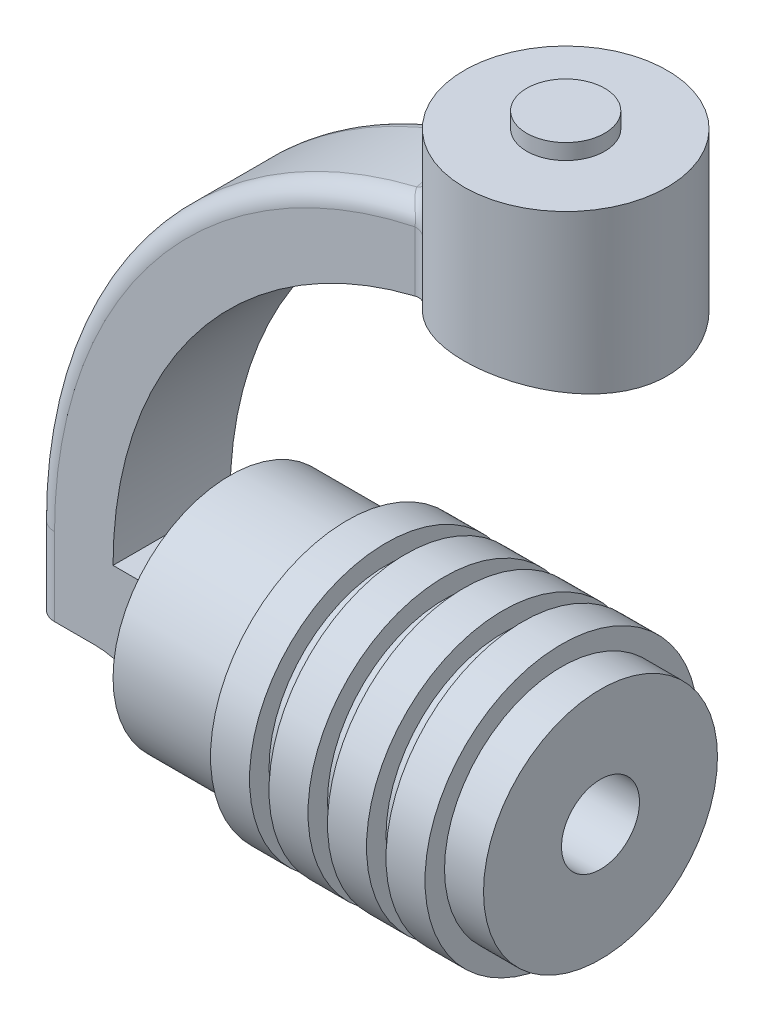
SolidWorks part; units mm, degrees
ref_plane "Front Plane" through (0, 0, 0) normal (0, 0, 1) x (1, 0, 0)
ref_plane "Top Plane" through (0, 0, 0) normal (0, 1, 0) x (1, 0, 0)
ref_plane "Right Plane" through (0, 0, 0) normal (1, 0, 0) x (0, 0, -1)
sketch "Sketch1" plane through (0, 0, 0) normal (0, 0, 1) x (1, 0, 0)
  line L0 (0, 0) -> (0, 190) construction
  line L1 (0, 0) -> (-110, 0) construction
  line L2 (-110, 0) -> (-110, 70)
  line L3 (26, 190) -> (-26, 190) construction
  line L4 (-130, 0) -> (-130, 70)
  line L5 (-25.2921, 170.0125) -> (-28.5836, 189.7398)
  line L6 (-130, 0) -> (-130, -40)
  line L7 (-130, -40) -> (-90, -40)
  line L8 (-90, -40) -> (-90, -20)
  line L9 (-90, -20) -> (-110, -20)
  line L10 (-110, -20) -> (-110, 0)
  arc A0 (-110, 70) -> (-25.2921, 170.0125) centre (-8.6049, 70) cw
  arc A1 (-130, 70) -> (-28.5836, 189.7398) centre (-8.6049, 70) cw
  point P8 (0, 190)
  dimension "D1" = 190
  dimension "D2" = 110
  dimension "D3" = 70
  dimension "D4" = 52
  dimension "D5" = 20
  dimension "D7" = 40
  dimension "D8" = 40
  dimension "D6" = 20
extrude "Boss-Extrude1" add sketch "Sketch1" along normal blind 30
sketch "Sketch2" plane through (-90, 0, 0) normal (1, 0, 0) x (0, 0, -1)
  line L0 (0, -30) -> (-30, -30) construction
  line L1 (0, -40) -> (0, -20) construction
  line L2 (-30, -40) -> (-30, -20) construction
  circle A0 centre (-15, -30) radius 30
  dimension "D1" = 60
extrude "Boss-Extrude2" add sketch "Sketch2" along normal blind 90 and the other way blind 5
sketch "Sketch3" plane through (0, 0, 0) normal (1, 0, 0) x (0, 0, -1)
  circle A0 centre (-15, -30) radius 35
  dimension "D1" = 70
extrude "Boss-Extrude3" add sketch "Sketch3" against normal blind 10 from offset 10 offset against normal yes
pattern_linear "LPattern1" count 4 spacing 15 along (-1, 0, 0) of "Boss-Extrude3"
sketch "Sketch4" plane through (0, 0, 0) normal (1, 0, 0) x (0, 0, -1)
  circle A0 centre (-15, -30) radius 10
  dimension "D1" = 20
extrude "Cut-Extrude1" cut sketch "Sketch4" against normal blind 20
ref_plane "Plane1" through (0, 190, 0) normal (0, 1, 0) x (1, 0, 0)
sketch "Sketch5" plane through (0, 190, 0) normal (0, 1, 0) x (1, 0, 0)
  line L0 (-28.5836, -15) -> (10.7464, -15) construction
  line L1 (-28.5836, -30) -> (-28.5836, 0) construction
  circle A0 centre (-8.9186, -15) radius 26
  dimension "D2" = 52
  dimension "D1" = 39.33
extrude "Boss-Extrude4" add sketch "Sketch5" along normal blind 20 and the other way up to surface other way up to face at (-76.8116, 127.7693, 15)
sketch "Sketch6" plane through (0, 210, 0) normal (0, 1, 0) x (1, 0, 0)
  circle A0 centre (-8.9186, -15) radius 10
  dimension "D1" = 20
extrude "Boss-Extrude5" add sketch "Sketch6" along normal blind 4
fillet "Fillet1" radius 20 1 edges at (-95, -40, 15)
fillet "Fillet2" radius 5 8 edges at (-30.1554, 179.2727, 30) (-30.1554, 179.2727, 0) (-130, 15, 0) (-101.7523, 147.8481, 30) (-34.8815, 188.5171, 13.6115) (-101.7523, 147.8481, 0) (-130, 15, 30) (-130, -40, 15)
sketch "Sketch8" plane through (0, 0, 30) normal (0, 0, 1) x (1, 0, 0)
  line L0 (-110, 70) -> (-129.4282, 70)
  line L2 (-129.4282, 70) -> (-159.144, 70)
  line L3 (-159.144, 70) -> (-159.144, -70.7775)
  line L4 (-159.144, -70.7775) -> (71.3188, -70.7775)
  line L5 (71.3188, -70.7775) -> (71.3188, 70)
  line L6 (71.3188, 70) -> (-110, 70)
extrude "Cut-Extrude2" cut sketch "Sketch8" against normal through all both and the other way through all
sketch "Sketch9" plane through (0, 70, 0) normal (0, -1, 0) x (1, 0, 0)
  line L4 (-125, 0) -> (-110, 0)
  line L5 (-110, 0) -> (-110, 30)
  line L6 (-110, 30) -> (-125, 30)
  line L7 (-130, 25) -> (-130, 5)
  line L8 (-125, 0) -> (-110, 0)
  line L9 (-110, 0) -> (-110, 30)
  line L10 (-110, 30) -> (-125, 30)
  line L11 (-130, 25) -> (-130, 5)
  arc A2 (-125, 30) -> (-130, 25) centre (-125, 25) ccw
  arc A3 (-130, 5) -> (-125, 0) centre (-125, 5) ccw
  arc A4 (-125, 30) -> (-130, 25) centre (-125, 25) ccw
  arc A5 (-130, 5) -> (-125, 0) centre (-125, 5) ccw
  dimension "D1" = 0
extrude "Boss-Extrude6" add sketch "Sketch9" along normal blind 20
sketch "Sketch10" plane through (-110, 0, 0) normal (1, 0, 0) x (0, 0, -1)
  line L4 (0, 70) -> (-30, 70)
  line L5 (-30, 70) -> (-30, 50)
  line L6 (-30, 50) -> (0, 50)
  line L7 (0, 50) -> (0, 70)
  line L8 (0, 70) -> (-30, 70)
  line L9 (-30, 70) -> (-30, 50)
  line L10 (-30, 50) -> (0, 50)
  line L11 (0, 50) -> (0, 70)
  dimension "D1" = 0
extrude "Boss-Extrude7" add sketch "Sketch10" along normal blind 20
sketch "Sketch11" plane through (-90, 0, 0) normal (1, 0, 0) x (0, 0, -1)
  line L0 (0, 60) -> (-30, 60) construction
  line L1 (0, 50) -> (0, 70) construction
  line L2 (-30, 70) -> (-30, 50) construction
  circle A0 centre (-15, 60) radius 30
  dimension "D1" = 60
extrude "Boss-Extrude8" add sketch "Sketch11" along normal blind 90 and the other way blind 5
sketch "Sketch12" plane through (0, 0, 0) normal (1, 0, 0) x (0, 0, -1)
  circle A0 centre (-15, 60) radius 35
  dimension "D1" = 70
extrude "Boss-Extrude9" add sketch "Sketch12" against normal blind 10 from offset 10 offset against normal yes
pattern_linear "LPattern2" count 4 spacing 15 along (-1, 0, 0) of "Boss-Extrude9"
sketch "Sketch13" plane through (0, 0, 0) normal (1, 0, 0) x (0, 0, -1)
  circle A0 centre (-15, 60) radius 10
  dimension "D1" = 20
extrude "Cut-Extrude3" cut sketch "Sketch13" against normal blind 20
fillet "Fillet3" radius 20 1 edges at (-95, 50, 15)
